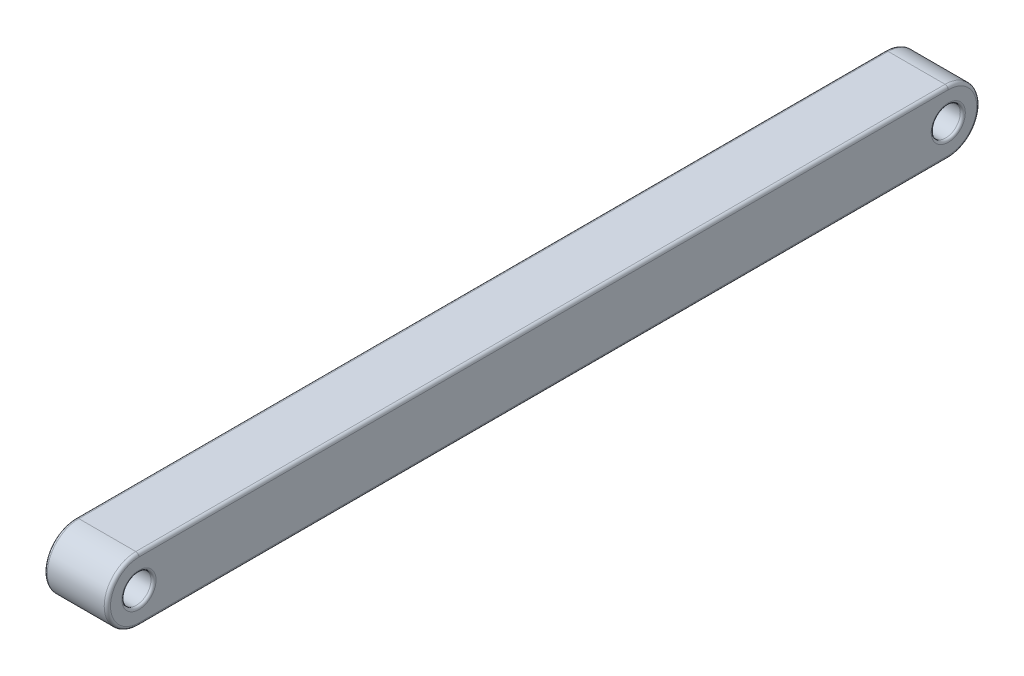
SolidWorks part; units mm, degrees
ref_plane "Front Plane" through (0, 0, 0) normal (0, 0, 1) x (1, 0, 0)
ref_plane "Top Plane" through (0, 0, 0) normal (0, 1, 0) x (1, 0, 0)
ref_plane "Right Plane" through (0, 0, 0) normal (1, 0, 0) x (0, 0, -1)
sketch "Sketch1" plane through (0, 0, 0) normal (1, 0, 0) x (0, 0, -1)
  line L1 (0, 0) -> (30, 0)
  line L2 (0, 0) -> (0, -2.5) construction
  line L3 (0, -2.5) -> (30, -2.5)
  line L4 (30, 0) -> (30, -2.5) construction
  line L5 (0, 0) -> (-1, 0)
  line L6 (0, 0) -> (0, -2.5) construction
  line L7 (0, -2.5) -> (-1, -2.5)
  line L8 (-1, 0) -> (-1, -2.5) construction
  line L9 (30, 0) -> (31, 0)
  line L10 (30, 0) -> (30, -2.5) construction
  line L11 (30, -2.5) -> (31, -2.5)
  line L12 (31, 0) -> (31, -2.5) construction
  line L16 (0, -1.25) -> (-1, -1.25) construction
  line L17 (30, -1.25) -> (31, -1.25) construction
  circle A0 centre (-1, -1.25) radius 0.575
  arc A1 (-1, -2.5) -> (-1, 0) centre (-1, -1.25) cw
  circle A2 centre (31, -1.25) radius 0.575
  arc A3 (31, 0) -> (31, -2.5) centre (31, -1.25) cw
  dimension "D1" = 1.15
  dimension "D4" = 1.15
  dimension "D2" = 2.5
  dimension "D3" = 2.5
  dimension "D5" = 32
  dimension "D6" = 2.5
  dimension "D7" = 1
  dimension "D8" = 1
extrude "Boss-Extrude1" add sketch "Sketch1" along normal blind 2.5 contours A3 L9 L1 L5 A1 L7 L3 L11 A2 A0 region at (0, -1.25, -15)
fillet "Fillet1" radius 0.125 8 edges at (2.5, -1.25, -32.25) (2.5, 0, -15) (2.5, -1.25, 2.25) (0, -1.25, -32.25) (0, 0, -15) (0, -1.25, 2.25) (2.5, -2.5, -15) (0, -2.5, -15)
fillet "Fillet2" radius 0.1 4 edges at (0, -1.25, -31.575) (2.5, -1.25, -31.575) (0, -1.25, 0.425) (2.5, -1.25, 0.425)
